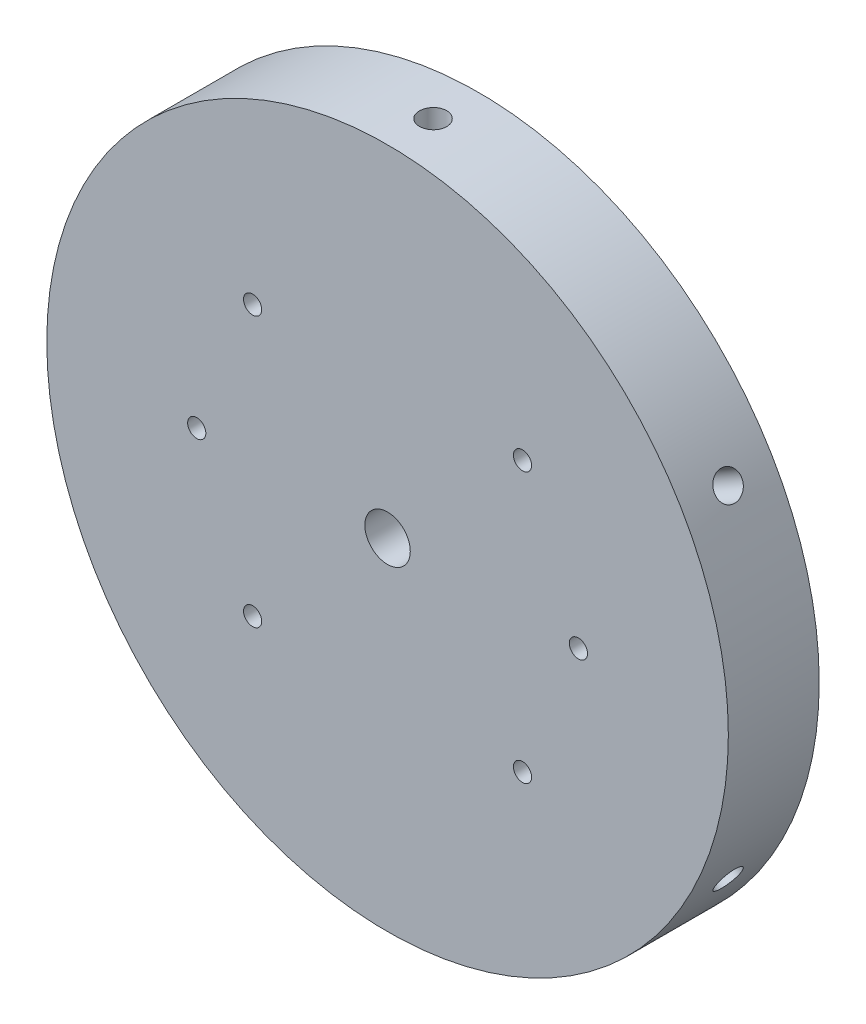
SolidWorks part; units mm, degrees
ref_plane "前基準面" through (0, 0, 0) normal (0, 0, 1) x (1, 0, 0)
ref_plane "上基準面" through (0, 0, 0) normal (0, 1, 0) x (1, 0, 0)
ref_plane "右基準面" through (0, 0, 0) normal (1, 0, 0) x (0, 0, -1)
ref_axis "基準軸1" through (0, -55, 0) along (0, 1, 0)
ref_axis "基準軸2" through (-88.99, 0, 0) along (1, 0, 0)
ref_axis "基準軸3" through (0, 0, -88.99) along (0, 0, 1)
sketch "草圖1" plane through (0, 0, 0) normal (0, 0, 1) x (1, 0, 0)
  circle A0 centre (0, 0) radius 75
  dimension "D1" = 150
extrude "填料-伸長1" add sketch "草圖1" along normal blind 20
ref_plane "平面1" through (0, 0, 0) normal (-0.7071, 0.7071, 0) x (0, 0, 1)
hole_wizard "Ø4.0mm 定位孔1" positions "草圖3" profile "草圖4" hole size "Ø4.0" standard "JIS" end condition up to next
sketch "草圖3" plane through (0, 0, 20) normal (0, 0, 1) x (1, 0, 0)
  line L0 (69.218, 69.218) -> (-69.218, -69.218) construction
  point P0 (29.6985, 29.6985)
  dimension "D1" = 42
sketch "草圖4" plane through (29.6985, 29.6985, 20) normal (1, 0, 0) x (0, -1, 0)
  line L0 (0, 0) -> (0, 20.001)
  line L1 (0, 20.001) -> (2, 20.001)
  line L2 (2, 20.001) -> (2, 0)
  line L5 (2, 0) -> (0, 0)
  line L11 (0, -6.35) -> (0, 107.95) construction
  dimension "貫穿孔直徑" = 4
  dimension "貫穿孔深度" = 20.001
pattern_circular "環狀複製排列1" count 4 over 360 about axis through (0, 0, -88.99) along (0, 0, 1) of "Ø4.0mm 定位孔1"
ref_plane "平面2" through (0, 75, 0) normal (0, 1, 0) x (1, 0, 0)
hole_wizard "Ø6.0mm 定位孔1" positions "草圖5" profile "草圖6" hole size "Ø6.0" standard "JIS"
sketch "草圖5" plane through (0, 75, 0) normal (0, 1, 0) x (1, 0, 0)
  line L0 (0, -11) -> (0, 11) construction
  point P0 (0, -10)
  dimension "D1" = 10
sketch "草圖6" plane through (0, 75, 10) normal (1, 0, 0) x (0, 0, 1)
  line L0 (0, 0) -> (0, 21.8026)
  line L1 (0, 21.8026) -> (3, 20)
  line L2 (3, 20) -> (3, 0)
  line L5 (3, 0) -> (0, 0)
  line L10 (0, 21.8026) -> (-3, 20) construction
  line L11 (0, -6.35) -> (0, 107.95) construction
  dimension "鑽孔直徑" = 6
  dimension "鑽孔深度" = 20
  dimension "導頭角度" = 118
pattern_circular "環狀複製排列2" count 6 over 360 about axis through (0, 0, -88.99) along (0, 0, 1) of "Ø6.0mm 定位孔1"
sketch "草圖7" plane through (0, 0, 20) normal (0, 0, 1) x (1, 0, 0)
  circle A0 centre (0, 0) radius 5
  dimension "D1" = 10
extrude "除料-伸長1" cut sketch "草圖7" against normal up to next
cosmetic thread "裝飾螺紋線1" parameters "D2"=12
hole_wizard "Ø4.0mm 定位孔2" positions "草圖10" profile "草圖9" hole size "Ø4.0" standard "JIS" end condition up to next
sketch "草圖10" plane through (0, 0, 20) normal (0, 0, 1) x (1, 0, 0)
  line L0 (11, 0) -> (-11, 0) construction
  point P0 (-42, 0)
  dimension "D1" = 42
sketch "草圖9" plane through (-42, 0, 20) normal (1, 0, 0) x (0, -1, 0)
  line L0 (0, 0) -> (0, 20.001)
  line L1 (0, 20.001) -> (2, 20.001)
  line L2 (2, 20.001) -> (2, 0)
  line L5 (2, 0) -> (0, 0)
  line L11 (0, -6.35) -> (0, 107.95) construction
  dimension "貫穿孔直徑" = 4
  dimension "貫穿孔深度" = 20.001
pattern_circular "環狀複製排列3" count 2 over 360 about axis through (0, 0, -0.001) along (0, 0, 1) of "Ø4.0mm 定位孔2" reverse direction yes
